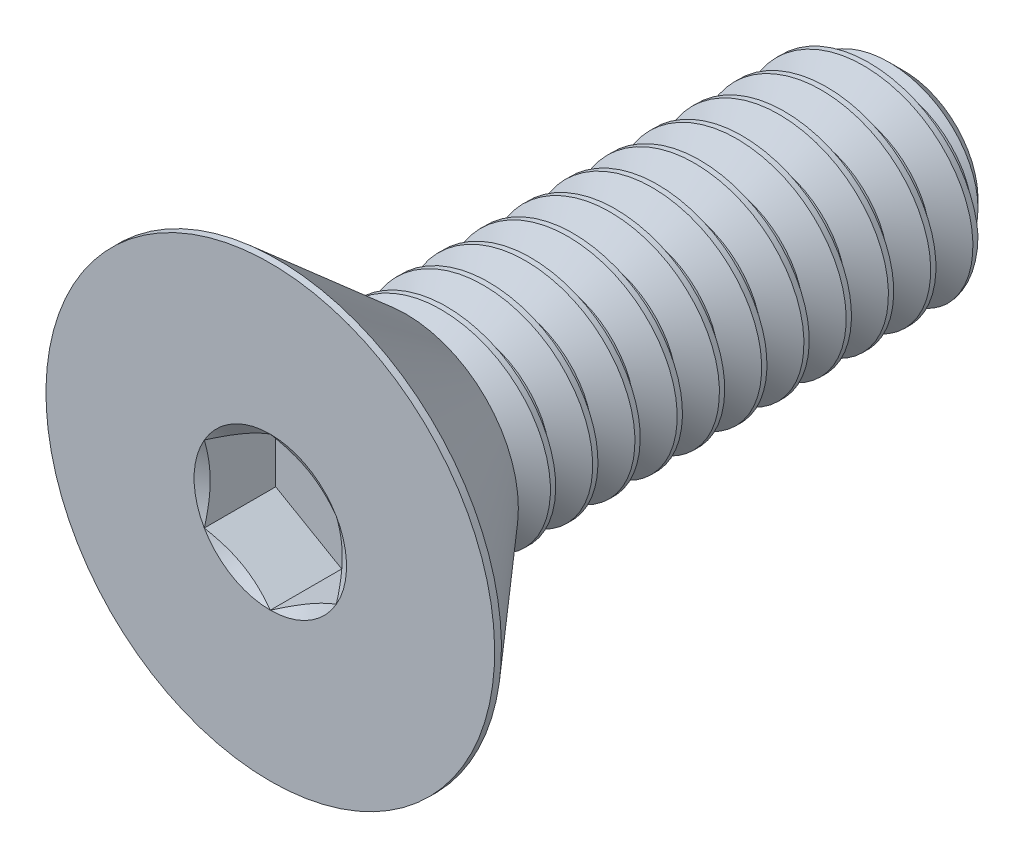
SolidWorks part; units mm, degrees
ref_plane "Front Plane" through (0, 0, 0) normal (0, 0, 1) x (1, 0, 0)
ref_plane "Top Plane" through (0, 0, 0) normal (0, 1, 0) x (1, 0, 0)
ref_plane "Right Plane" through (0, 0, 0) normal (1, 0, 0) x (0, 0, -1)
sketch "Sketch1" plane through (0, 0, 0) normal (1, 0, 0) x (0, 0, -1)
  line L0 (-9.525, 0) -> (9.525, 0) construction
  line L1 (9.525, 0) -> (9.525, 3.175) construction
  line L2 (9.525, 3.175) -> (-4.9232, 3.175) construction
  line L3 (-9.525, 6.7437) -> (-9.3205, 6.7437) construction
  line L4 (-9.525, 6.7437) -> (-9.525, 0) construction
  line L6 (-9.3205, 6.7437) -> (-5.4356, 3.3666) construction
  line L7 (9.525, 2.2225) -> (8.5725, 3.175) construction
  line L8 (9.4456, 3.3125) -> (10.0806, 2.2126) construction
  line L9 (10.0806, 2.2126) -> (10.7156, 3.3125) construction
  line L10 (10.7156, 3.3125) -> (9.4456, 3.3125) construction
  line L11 (10.0806, 3.3125) -> (10.0806, 3.175) construction
  line L12 (10.0806, 2.2126) -> (10.0806, 2.3501) construction
  line L13 (10.0012, 2.3501) -> (10.16, 2.3501) construction
  line L14 (9.525, 3.175) -> (10.6362, 3.175) construction
  line L15 (9.4853, 3.2437) -> (10.6759, 3.2437) construction
  line L18 (-9.3205, -6.7437) -> (-5.4356, -3.3666) construction
  line L19 (-4.9232, 3.175) -> (-5.4356, 3.175) construction
  line L20 (-5.4356, 3.175) -> (-5.4356, 3.3666) construction
  arc A0 (-4.9232, 3.175) -> (-5.4356, 3.3666) centre (-4.9232, 3.956) cw construction
  point P3 (-5.1794, 3.175)
  point P4 (0, 0)
  point P25 (10.0806, 2.3501)
  point P28 (10.0806, 3.175)
  point P31 (10.0806, 3.2437)
  point P40 (9.525, -3.175)
  point P45 (-7.3781, 5.0551)
  point P50 (7.62, -3.175)
  dimension "Length" = 19.05
  dimension "Screw Size Decimal Equivalent" = 6.35
  dimension "D2" = 0.1588
  dimension "Thread Pitch" = 1.27
  dimension "D3" = 0.9525
  dimension "Head Height" = 4.0894
  dimension "D7" = 45
  dimension "D8" = 0.2045
  dimension "D5" = 1.905
  dimension "Countersink Angle" = 82
  dimension "Head Diameter" = 13.4874
sketch "Sketch2" plane through (0, 0, 0) normal (0, 0, 1) x (1, 0, 0)
  line L0 (0, 2.2126) -> (0, 3.3125) construction
  line L1 (0, 2.2914) -> (-1.9844, 1.1457) construction
  line L2 (-1.9844, 1.1457) -> (-1.9844, -1.1457) construction
  line L3 (-1.9844, -1.1457) -> (0, -2.2914) construction
  line L4 (0, -2.2914) -> (1.9844, -1.1457) construction
  line L5 (1.9844, -1.1457) -> (1.9844, 1.1457) construction
  line L6 (1.9844, 1.1457) -> (0, 2.2914) construction
  circle A0 centre (0, 0) radius 1.9844 construction
  circle A1 centre (0, 0) radius 2.2914 construction
  circle A2 centre (0, 0) radius 6.7437 construction
  dimension "Head Diameter" = 13.4874
  dimension "Drive Size" = 3.9688
sketch "Sketch3" plane through (0, 0, 0) normal (1, 0, 0) x (0, 0, -1)
  line L0 (-9.525, 0) -> (9.525, 0)
  line L1 (9.525, 0) -> (9.525, 2.2225)
  line L2 (9.525, 2.2225) -> (8.5725, 3.175)
  line L3 (8.5725, 3.175) -> (-5.4356, 3.175)
  line L6 (-9.525, 6.7437) -> (-9.525, 0)
  line L10 (-9.525, 6.7437) -> (-9.3205, 6.7437) construction
  line L11 (-9.3205, 6.7437) -> (-5.4356, 3.3666) construction
  line L12 (-9.525, 6.7437) -> (-9.3205, 6.7437)
  line L13 (-9.3205, 6.7437) -> (-5.4356, 3.3666)
  line L14 (-5.4356, 3.3666) -> (-5.4356, 3.175)
revolve "Revolve1" add sketch "Sketch3" angle 360 about L0
sketch "Sketch4" plane through (0, 0, 9.525) normal (0, 0, 1) x (1, 0, 0)
  line L0 (1.9844, -1.1457) -> (1.9844, 1.1457) construction
  line L1 (0, -2.2914) -> (1.9844, -1.1457) construction
  line L2 (-1.9844, -1.1457) -> (0, -2.2914) construction
  line L3 (-1.9844, 1.1457) -> (-1.9844, -1.1457) construction
  line L4 (0, 2.2914) -> (-1.9844, 1.1457) construction
  line L5 (1.9844, 1.1457) -> (0, 2.2914) construction
  line L6 (1.9844, -1.1457) -> (1.9844, 1.1457)
  line L7 (0, -2.2914) -> (1.9844, -1.1457)
  line L8 (-1.9844, -1.1457) -> (0, -2.2914)
  line L9 (-1.9844, 1.1457) -> (-1.9844, -1.1457)
  line L10 (0, 2.2914) -> (-1.9844, 1.1457)
  line L11 (1.9844, 1.1457) -> (0, 2.2914)
extrude "Cut-Extrude1" cut sketch "Sketch4" against normal up to vertex (2.1469 mm away) up to point (0, 5.0551, 7.3781)
sketch "Sketch6" plane through (0, 0, 9.525) normal (0, 0, 1) x (1, 0, 0)
  circle A0 centre (0, 0) radius 2.2914 construction
  circle A1 centre (0, 0) radius 2.2914
extrude "Cut-Extrude2" cut sketch "Sketch6" against normal up to vertex (2.1469 mm away) draft 60 up to point (0, 5.0551, 7.3781)
ref_plane "Plane1" through (0, 0, 5.4356) normal (0, 0, 1) x (1, 0, 0)
split "Split1" trim tools "Plane1" bodies to split 106 resulting bodies 107 108
sketch "Sketch7" plane through (0, 0, -9.525) normal (0, 0, -1) x (-1, 0, 0)
  circle A0 centre (0, 0) radius 3.175
curve "Helix/Spiral1" pitch 1.27 height 20.32 radius 3.175 centre (0, 0, -9.525) axis (0, 0, 1) start towards (0, 1, 0)
sketch "Sketch8" plane through (0, 0, 0) normal (1, 0, 0) x (0, 0, -1)
  line L0 (9.4853, 3.2437) -> (10.6759, 3.2437)
  line L1 (10.6759, 3.2437) -> (10.16, 2.3501)
  line L2 (10.16, 2.3501) -> (10.0012, 2.3501)
  line L3 (10.0012, 2.3501) -> (9.4853, 3.2437)
sweep "Cut-Sweep1" cut profiles "Sketch8" path "Helix/Spiral1" align with end faces yes
combine bodies "Combine2" operation type add bodies to combine 107 109
equation "\"D2@Sketch1\" = \"Thread Pitch@Sketch1\" / 8"
equation "\"D3@Sketch1\" = \"Thread Pitch@Sketch1\" * 0.75"
equation "\"D3@Helix/Spiral1\" = \"Length@Sketch1\" + \"Thread Pitch@Sketch1\""
equation "\"D4@Helix/Spiral1\" = \"Thread Pitch@Sketch1\""
equation "\"D8@Sketch1\"=\"Head Height@Sketch1\"*0.05"
equation "\"D1\"= \"Head Height@Sketch1\" * 0.075"
equation "\"D5@Sketch1\" = \"Thread Pitch@Sketch1\" * 1.5"
equation "\"Head Diameter@Sketch1\"=\"Head Diameter@Sketch2\""
